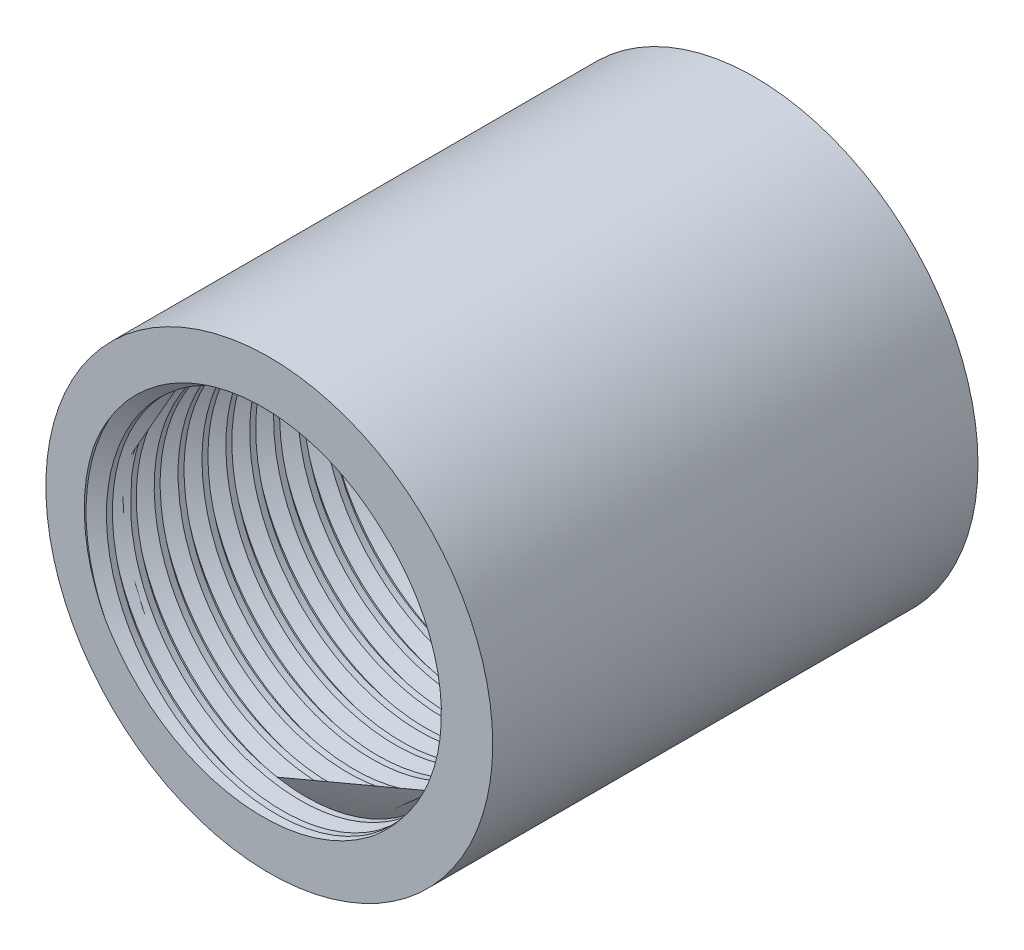
SolidWorks part; units mm, degrees
ref_plane "Płaszczyzna przednia" through (0, 0, 0) normal (0, 0, 1) x (1, 0, 0)
ref_plane "Płaszczyzna górna" through (0, 0, 0) normal (0, 1, 0) x (1, 0, 0)
ref_plane "Płaszczyzna prawa" through (0, 0, 0) normal (1, 0, 0) x (0, 0, -1)
sketch "Szkic1" plane through (0, 0, 0) normal (0, 0, 1) x (1, 0, 0)
  circle A0 centre (0, 0) radius 19.8
  circle A1 centre (0, 0) radius 15.25
  dimension "D1" = 39.6
  dimension "D2" = 30.5
extrude "Dodanie-wyciągnięcie1" add sketch "Szkic1" along normal blind 43
thread "Gwint1" pitch 2.1167 method cut trim with start face yes trim with end face yes profile "Profil gwintu1" start angle 0, offset 5, length 0, pitch 2.1167, diameter 30.5
ref_plane "Płaszczyzna1" through (-15.25, 0, 48) normal (0, -1, 0) x (-1, 0, 0)
sketch "Profil gwintu1" plane through (-15.25, 0, 48) normal (0, -1, 0) x (-1, 0, 0)
  line L0 (0, 0) -> (0, 2.1167) construction
  line L1 (0, 0) -> (1.1457, 0.6615)
  line L2 (1.1457, 0.6615) -> (1.1457, 0.926)
  line L3 (1.1457, 0.926) -> (0, 1.5875)
  line L4 (1.1457, 0.7937) -> (0, 0.7937) construction
  line L11 (0, 0) -> (0, 1.5875)
  point P2 (0, 0)
  dimension "Pitch" = 2.1167
  dimension "Profile_Angle" = 60
  dimension "Profile_Land" = 0.2646
  dimension "Profile_Height" = 1.1457
